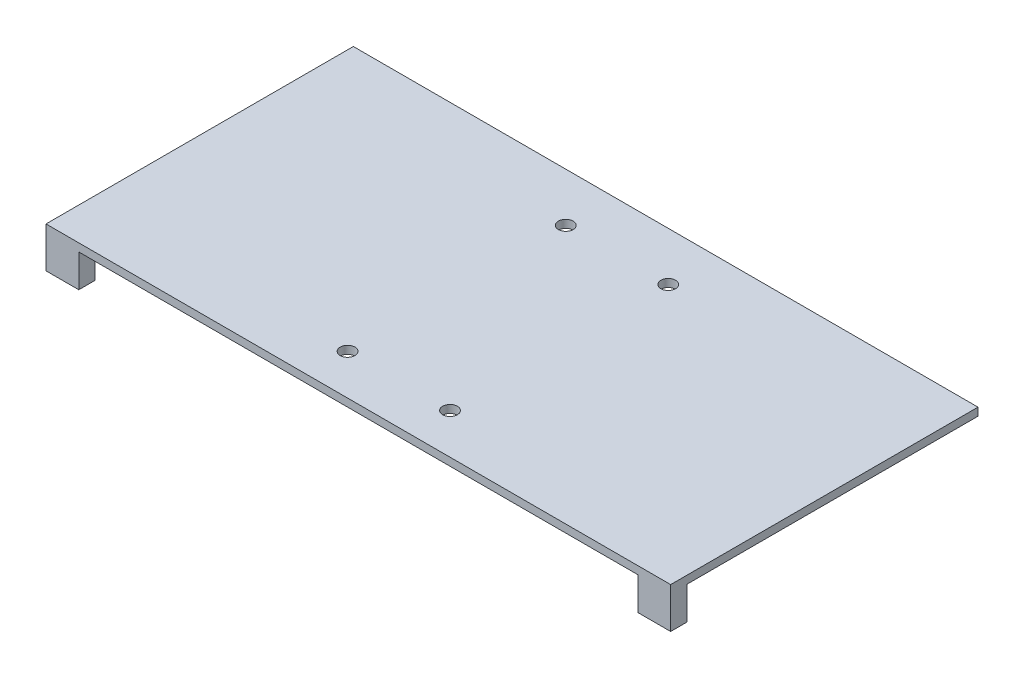
SolidWorks part; units mm, degrees
material "Thornel Mat VMA"
ref_plane "Front Plane" through (0, 0, 0) normal (0, 0, 1) x (1, 0, 0)
ref_plane "Top Plane" through (0, 0, 0) normal (0, 1, 0) x (1, 0, 0)
ref_plane "Right Plane" through (0, 0, 0) normal (1, 0, 0) x (0, 0, -1)
sketch "Sketch1" plane through (0, 0, 0) normal (0, 1, 0) x (1, 0, 0)
  line L1 (0, 0) -> (96.8, 0)
  line L2 (0, 0) -> (0, -47.625)
  line L3 (0, -47.625) -> (96.8, -47.625)
  line L4 (96.8, 0) -> (96.8, -47.625)
  dimension "D1" = 47.625
  dimension "D2" = 96.8
extrude "Boss-Extrude1" add sketch "Sketch1" along normal blind 1.2192
sketch "Sketch5" plane through (0, 1.2192, 0) normal (0, 1, 0) x (1, 0, 0)
  line L0 (96.8, 0) -> (0, 0) construction
  line L1 (56.3375, -7.5406) -> (40.4625, -7.5406) construction
  line L2 (0, 0) -> (0, -47.625) construction
  line L3 (96.8, -23.8125) -> (0, -23.8125) construction
  line L4 (96.8, -47.625) -> (96.8, 0) construction
  circle A0 centre (56.3375, -7.5406) radius 1.143
  circle A1 centre (40.4625, -7.5406) radius 1.143
  dimension "D1" = 2.286
  dimension "D2" = 2.286
  dimension "D3" = 15.875
  dimension "D4" = 7.5406
  dimension "D5" = 40.4625
extrude "Cut-Extrude1" cut sketch "Sketch5" against normal up to next
sketch "Sketch6" plane through (0, 1.2192, 0) normal (0, 1, 0) x (1, 0, 0)
  line L0 (56.3375, -41.3544) -> (40.4625, -41.3544) construction
  line L1 (0, 0) -> (0, -47.625) construction
  line L2 (0, -47.625) -> (96.8, -47.625) construction
  circle A0 centre (56.3375, -41.3544) radius 1.143
  circle A1 centre (40.4625, -41.3544) radius 1.143
  dimension "D1" = 2.286
  dimension "D2" = 2.286
  dimension "D3" = 15.875
  dimension "D4" = 6.2706
  dimension "D5" = 40.4625
extrude "Cut-Extrude2" cut sketch "Sketch6" against normal up to next
sketch "Sketch7" plane through (0, 0, 0) normal (0, -1, 0) x (-1, 0, 0)
  line L0 (-96.8, -47.625) -> (-96.8, -45.085)
  line L1 (-96.8, -47.625) -> (-96.8, 0) construction
  line L2 (-96.8, -45.085) -> (-91.72, -45.085)
  line L3 (-91.72, -45.085) -> (-91.72, -47.625)
  line L4 (0, -47.625) -> (-96.8, -47.625) construction
  line L5 (-91.72, -47.625) -> (-96.8, -47.625)
  line L6 (0, -47.625) -> (-5.08, -47.625)
  line L7 (-5.08, -47.625) -> (-5.08, -45.085)
  line L8 (0, -47.625) -> (0, -45.085)
  line L9 (0, 0) -> (0, -47.625) construction
  line L10 (0, -45.085) -> (-5.08, -45.085)
  dimension "D1" = 2.54
  dimension "D2" = 5.08
  dimension "D3" = 2.54
  dimension "D4" = 5.08
extrude "Boss-Extrude2" add sketch "Sketch7" along normal blind 5.08
